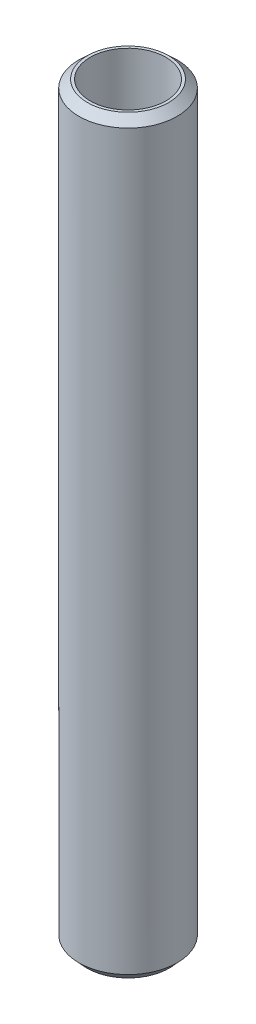
SolidWorks part; units mm, degrees
ref_plane "Front Plane" through (0, 0, 0) normal (0, 0, 1) x (1, 0, 0)
ref_plane "Top Plane" through (0, 0, 0) normal (0, 1, 0) x (1, 0, 0)
ref_plane "Right Plane" through (0, 0, 0) normal (1, 0, 0) x (0, 0, -1)
sketch "Sketch1" plane through (0, 0, 0) normal (0, 1, 0) x (1, 0, 0)
  circle A0 centre (0, 0) radius 22.5
  dimension "SHAFT_OD" = 45
extrude "Boss-Extrude1" add sketch "Sketch1" along normal blind 343.6665
sketch "Sketch2" plane through (0, 0, 0) normal (0, 1, 0) x (1, 0, 0)
  circle A0 centre (0, 0) radius 17.3613
  dimension "BORE_D" = 34.7226
extrude "Cut-Extrude1" cut sketch "Sketch2" along normal through all
chamfer "Chamfer1" distance 3.5677 angle 47.331 2 edges at (0, 343.6665, 22.5) (0, 0, 22.5) first distance on face at (0, 343.6665, 22.5) first distance on face at (0, 0, 17.3613)
